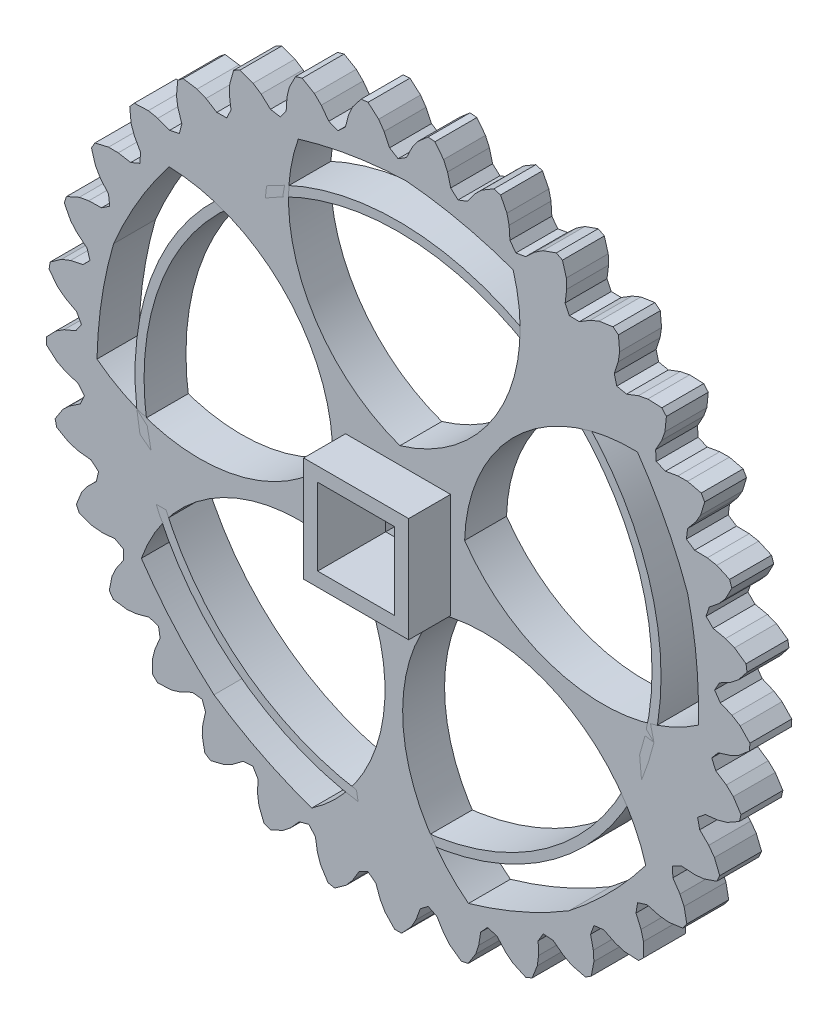
SolidWorks part; units mm, degrees
ref_plane "Front Plane" through (0, 0, 0) normal (0, 0, 1) x (1, 0, 0)
ref_plane "Top Plane" through (0, 0, 0) normal (0, 1, 0) x (1, 0, 0)
ref_plane "Right Plane" through (0, 0, 0) normal (1, 0, 0) x (0, 0, -1)
sketch "Sketch1" plane through (0, 0, 0) normal (0, 0, 1) x (1, 0, 0)
  line L1 (3.675, -3.675) -> (-3.675, -3.675)
  line L2 (3.675, -3.675) -> (3.675, 3.675)
  line L3 (3.675, 3.675) -> (-3.675, 3.675)
  line L4 (-3.675, -3.675) -> (-3.675, 3.675)
  circle A0 centre (0, 0) radius 33.6129
  point P3 (0, 3.675)
  point P9 (-3.675, 0)
  dimension "D1" = 67.2257
  dimension "D2" = 7.35
  dimension "D3" = 7.35
extrude "Boss-Extrude1" add sketch "Sketch1" along normal blind 4
sketch "Sketch2" plane through (0, 0, 0) normal (0, 0, 1) x (1, 0, 0)
  line L0 (0, 0) -> (0, 34.8589) construction
  line L1 (0, 30.2608) -> (-0.8069, 30.7591)
  line L2 (-0.8069, 30.7591) -> (-1.33, 31.849)
  line L3 (-1.33, 31.849) -> (-1.8557, 32.6046)
  line L4 (-1.8557, 32.6046) -> (-2.8665, 33.4904)
  line L5 (-2.8665, 33.4904) -> (-1.8557, 34.2629)
  line L6 (-1.8557, 34.2629) -> (0, 34.8589)
  line L7 (1.8557, 34.2629) -> (0, 34.8589)
  line L8 (2.8665, 33.4904) -> (1.8557, 34.2629)
  line L9 (1.8557, 32.6046) -> (2.8665, 33.4904)
  line L10 (1.33, 31.849) -> (1.8557, 32.6046)
  line L11 (0.8069, 30.7591) -> (1.33, 31.849)
  line L12 (0, 30.2608) -> (0.8069, 30.7591)
  circle A22 centre (0, 0) radius 33.6129 construction
  dimension "D5" = 0.5258
  dimension "D6" = 0.7556
  dimension "D9" = 0.5959
  dimension "D1" = 0.8069
  dimension "D2" = 0.4984
  dimension "D3" = 0.5231
  dimension "D4" = 1.0898
  dimension "D7" = 0.8858
  dimension "D8" = 1.8557
  dimension "D10" = 1.0107
  dimension "D11" = 0.7725
  dimension "D12" = 1.0107
extrude "Cut-Extrude1" cut sketch "Sketch2" along normal through all
pattern_circular "CirPattern1" count 33 over 360 about axis through (0, 0, 4) along (0, 0, -1) of "Cut-Extrude1"
sketch "Sketch3" plane through (0, 0, 0) normal (0, 0, 1) x (1, 0, 0)
  circle A0 centre (0, 0) radius 29.75
  dimension "D1" = 59.5
sketch "Sketch4" plane through (0, 0, 0) normal (0, 0, 1) x (1, 0, 0)
  line L0 (0, 0) -> (0.7854, 28.8152) construction
  arc A1 (0.7854, 28.8152) -> (-9.5267, 27.1273) centre (2.0438, -11.2177) ccw
  arc A2 (0.7854, 28.8152) -> (10.9903, 26.5681) centre (-2.6519, -11.0897) cw
  arc A4 (0.1805, 6.623) -> (-9.5267, 27.1273) centre (5.5791, 21.7288) cw
  arc A5 (0.1805, 6.623) -> (10.9903, 26.5681) centre (-4.3872, 22.0004) ccw
extrude "Cut-Extrude2" cut sketch "Sketch4" along normal through all both
sketch "Sketch5" plane through (0, 0, 0) normal (0, 0, 1) x (1, 0, 0)
  circle A0 centre (0, 0) radius 25.1098
  circle A1 centre (0, 0) radius 24.2496
extrude "Boss-Extrude2" add sketch "Sketch5" along normal through all separate body
pattern_circular "CirPattern2" count 5 over 360 about axis through (0, 0, 4) along (0, 0, -1) of "Cut-Extrude2" reverse direction yes
chamfer "Chamfer1" distance 1.5 distance2 0.5 4 edges at (-3.675, 0, 0) (0, -3.675, 0) (3.675, 0, 0) (0, 3.675, 0) first distance on face at (-3.675, 0, 2) first distance on face at (0, -3.675, 2) first distance on face at (3.675, 0, 2) first distance on face at (0, 3.675, 2)
sketch "Sketch6" plane through (0, 0, 4) normal (0, 0, 1) x (1, 0, 0)
  line L1 (-3.675, 3.675) -> (3.675, 3.675)
  line L2 (-3.675, 3.675) -> (-3.675, -3.675)
  line L3 (-3.675, -3.675) -> (3.675, -3.675)
  line L4 (3.675, 3.675) -> (3.675, -3.675)
  line L5 (-5.0131, 5.0131) -> (5.0131, 5.0131)
  line L6 (-5.0131, 5.0131) -> (-5.0131, -5.0131)
  line L7 (-5.0131, -5.0131) -> (5.0131, -5.0131)
  line L8 (5.0131, 5.0131) -> (5.0131, -5.0131)
  dimension "D1" = 1.3381
  dimension "D2" = 1.3381
  dimension "D3" = 1.3381
  dimension "D4" = 1.3381
extrude "Boss-Extrude3" add sketch "Sketch6" along normal blind 4
equation "\"padding\"=1.33807"
equation "\"D1@Sketch6\"=\"padding\""
equation "\"D2@Sketch6\"=\"padding\""
equation "\"D3@Sketch6\"=\"padding\""
equation "\"D4@Sketch6\"=\"padding\""
